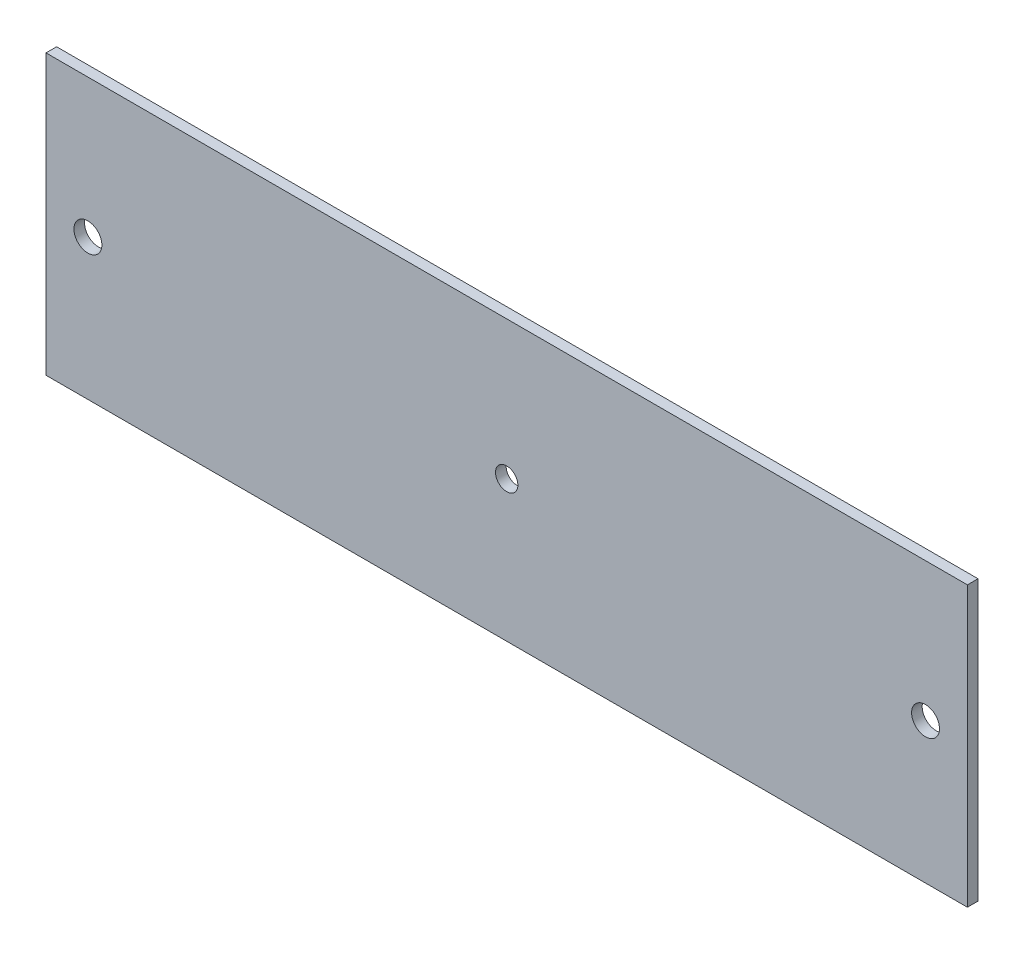
SolidWorks part; units mm, degrees
ref_plane "Front Plane" through (0, 0, 0) normal (0, 0, 1) x (1, 0, 0)
ref_plane "Top Plane" through (0, 0, 0) normal (0, 1, 0) x (1, 0, 0)
ref_plane "Right Plane" through (0, 0, 0) normal (1, 0, 0) x (0, 0, -1)
sketch "Sketch2" plane through (0, 0, 0) normal (0, 0, 1) x (1, 0, 0)
  line L1 (-35.4064, 34.3768) -> (129.5936, 34.3768)
  line L2 (-35.4064, 34.3768) -> (-35.4064, -15.6232)
  line L3 (-35.4064, -15.6232) -> (129.5936, -15.6232)
  line L4 (129.5936, 34.3768) -> (129.5936, -15.6232)
  dimension "D1" = 50
  dimension "D2" = 165
base flange "Base-Flange1" sketch "Sketch2" thickness 1.8974 reverse thickness direction no parameters "D1"=2.54
sketch "Sketch7" plane through (0, 0, -1.8974) normal (0, 0, -1) x (-1, 0, 0)
  line L0 (-129.5936, 34.3768) -> (35.4064, 34.3768) construction
  line L1 (-129.5936, -15.6232) -> (-129.5936, 34.3768) construction
  line L2 (35.4064, 34.3768) -> (35.4064, -15.6232) construction
  circle A0 centre (-122.0958, 9.5586) radius 2.5
  circle A1 centre (27.9064, 9.5715) radius 2.5
  circle A2 centre (-47.0936, 9.5715) radius 2
  point P6 (-47.0936, 34.3768)
  point P7 (-129.5936, 9.3768)
  dimension "D1" = 7.5
  dimension "D2" = 7.5
extrude "Cut-Extrude1" cut sketch "Sketch7" against normal blind 2 normal cut yes
sketch "Bend-Lines1" plane through (0, 0, 0) normal (0, 1, 0) x (1, 0, 0)
sketch "Bounding-Box1" plane through (0, 0, 0) normal (0, 1, 0) x (1, 0, 0)
sheet metal parameters "Sheet-Metal1" thickness 1.8974 parameters "D1"=2.54
flat pattern "Flat-Pattern1" [suppressed]
sketch "Bend-Lines2" plane through (0, 0, 0) normal (0, 1, 0) x (1, 0, 0)
sketch "Bounding-Box2" [suppressed] plane through (0, 0, 0) normal (0, 1, 0) x (1, 0, 0)
sheet metal parameters "Sheet-Metal2" thickness 1.8974 parameters "D1"=2.54
flat pattern "Flat-Pattern1"
sketch "Bend-Lines2" plane through (0, 0, 0) normal (0, 1, 0) x (1, 0, 0)
sketch "Bounding-Box2" [suppressed] plane through (0, 0, 0) normal (0, 1, 0) x (1, 0, 0)
